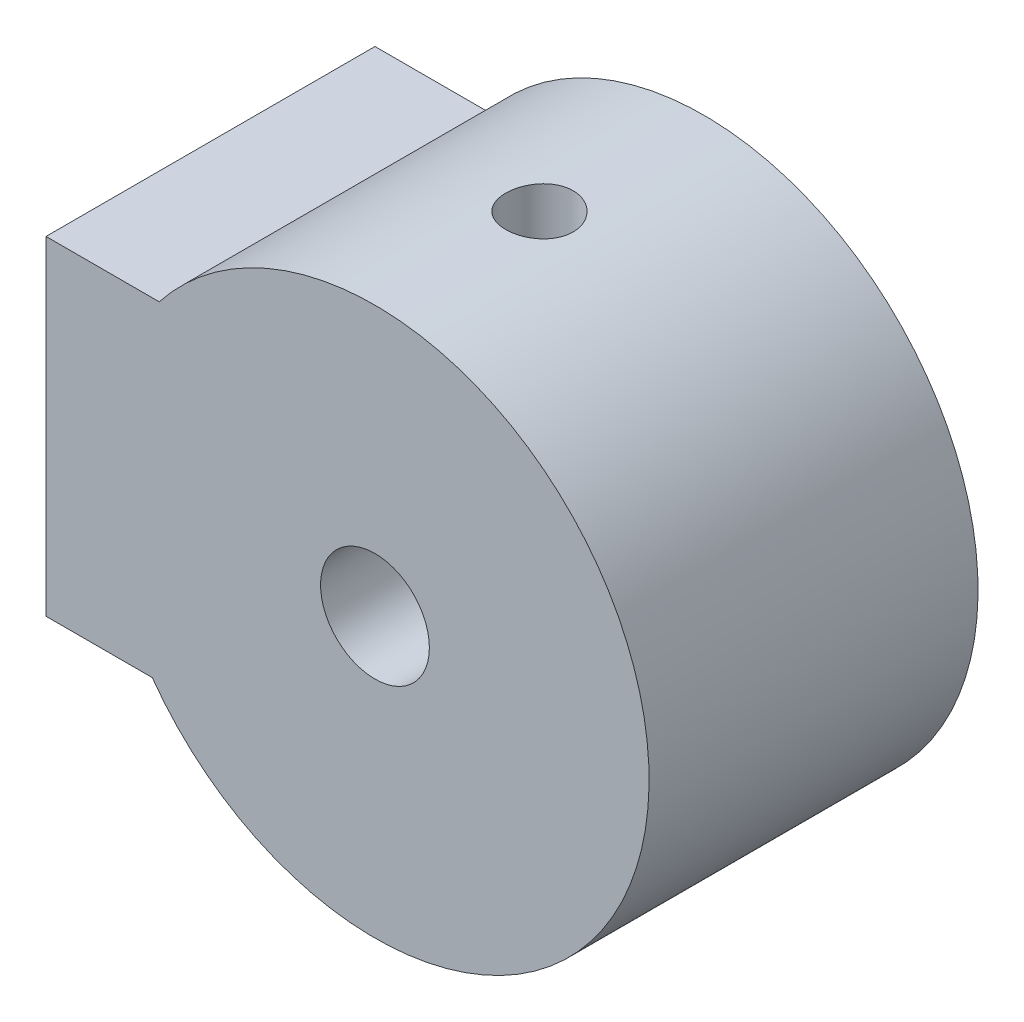
SolidWorks part; units mm, degrees
ref_plane "Front Plane" through (0, 0, 0) normal (0, 0, 1) x (1, 0, 0)
ref_plane "Top Plane" through (0, 0, 0) normal (0, 1, 0) x (1, 0, 0)
ref_plane "Right Plane" through (0, 0, 0) normal (1, 0, 0) x (0, 0, -1)
sketch "Sketch1" plane through (0, 0, 0) normal (0, 0, 1) x (1, 0, 0)
  line L0 (0, 0) -> (0, 19.05)
  line L1 (0, 19.05) -> (19.05, 19.05)
  line L2 (19.05, 19.05) -> (19.05, 0)
  line L3 (19.05, 0) -> (0, 0)
  circle A0 centre (19.05, 9.525) radius 9.525
  circle A1 centre (19.05, 9.525) radius 3.15
  circle A2 centre (19.05, 9.256) radius 15.875
  dimension "D3" = 6.3
  dimension "D4" = 31.75
  dimension "D1" = 19.05
  dimension "D2" = 19.05
extrude "Boss-Extrude1" add sketch "Sketch1" along normal blind 19.05 contours A1 L2 A0 | A1 L2 A0 | A0 L1 L0 L3 | A2 L1 L0 L3 | L3 A2 L1 A0 region at (2.1997, 9.6639, 0) region at (8.1262, 9.4461, 0) region at (12.6013, -0.4285, 0) region at (14.6752, 9.525, 0) region at (23.4248, 9.525, 0)
ref_plane "Plane1" through (0, 25.4, 0) normal (0, 1, 0) x (1, 0, 0)
sketch "Sketch3" plane through (0, 19.05, 0) normal (0, 1, 0) x (1, 0, 0)
  line L4 (6.5562, 0) -> (0, 0)
  line L5 (0, 0) -> (0, -19.05)
  line L6 (0, -19.05) -> (6.5562, -19.05)
  line L7 (6.5562, -19.05) -> (6.5562, 0)
  line L8 (6.5562, 0) -> (0, 0)
  line L9 (0, 0) -> (0, -19.05)
  line L10 (0, -19.05) -> (6.5562, -19.05)
  line L11 (6.5562, -19.05) -> (6.5562, 0)
  line L12 (6.1527, -19.05) -> (34.925, -19.05) construction
  line L13 (6.1527, -19.05) -> (34.925, -19.05)
  line L14 (19.05, -17.4979) -> (19.05, -1.3096) construction
  line L15 (6.5562, -9.525) -> (19.05, -9.525) construction
  line L16 (15.9, -19.05) -> (22.2, -19.05) construction
  line L17 (15.9, -19.05) -> (22.2, -19.05)
  line L18 (15.9, -17.4979) -> (22.2, -17.4979) construction
  circle A0 centre (19.05, -9.525) radius 1.95
  point P15 (19.05, -17.2311)
  point P16 (24.3943, -17.4979)
  point P17 (18.7647, -1.3096)
  point P18 (0, 0)
  point P19 (0, 0)
  dimension "D2" = 3.9
  dimension "D1" = 0
extrude "Cut-Extrude2" cut sketch "Sketch3" against normal up to surface (12.725 mm away) from surface contours A0 region at (19.05, 19.05, 9.525) up to face at (22.2, 9.525, 19.05) starting at plane "Plane1"
